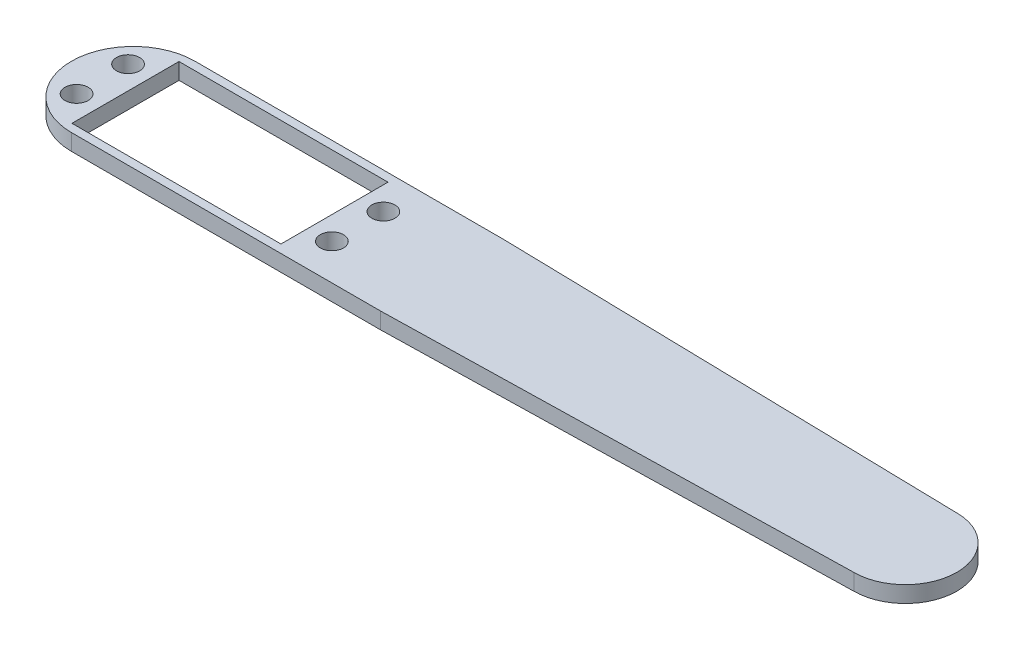
SolidWorks part; units mm, degrees
ref_plane "Front Plane" through (0, 0, 0) normal (0, 0, 1) x (1, 0, 0)
ref_plane "Top Plane" through (0, 0, 0) normal (0, 1, 0) x (1, 0, 0)
ref_plane "Right Plane" through (0, 0, 0) normal (1, 0, 0) x (0, 0, -1)
sketch "Sketch1" plane through (0, 0, 0) normal (0, 1, 0) x (1, 0, 0)
  line L0 (-141.2397, 14.2447) -> (-81.2397, 14.2447)
  line L1 (-81.2397, 14.2447) -> (8.7603, 12.2447)
  line L2 (-141.2397, -9.7553) -> (-81.2397, -9.7553)
  line L3 (-81.2397, -9.7553) -> (8.7603, -7.7553)
  line L4 (-147.2397, 19.311) -> (-147.2397, -13.0468) construction
  line L6 (-142.7397, -8.1553) -> (-102.1397, -8.1553)
  line L7 (-142.7397, -8.1553) -> (-142.7397, 12.6447)
  line L8 (-142.7397, 12.6447) -> (-102.1397, 12.6447)
  line L9 (-102.1397, -8.1553) -> (-102.1397, 12.6447)
  arc A0 (-141.2397, 14.2447) -> (-141.2397, -9.7553) centre (-141.2397, 2.2447) ccw
  arc A1 (8.7603, -7.7553) -> (8.7603, 12.2447) centre (8.7603, 2.2447) ccw
  circle A3 centre (-147.2397, 7.2447) radius 2.25
  circle A4 centre (-147.2397, -2.7553) radius 2.25
  circle A5 centre (-97.6397, 7.2447) radius 2.25
  circle A6 centre (-97.6397, -2.7553) radius 2.25
  dimension "D6" = 4.5
  dimension "D2" = 24
  dimension "D3" = 20
  dimension "D4" = 5
  dimension "D5" = 5
  dimension "D7" = 49.6
  dimension "D8" = 60
  dimension "D9" = 150
  dimension "D10" = 6
  dimension "D11" = 0
  dimension "D12" = 20.8
  dimension "D13" = 40.6
extrude "Boss-Extrude1" add sketch "Sketch1" along normal blind 3.175
equation "\"D5@Sketch1\"=\"D4@Sketch1\""
